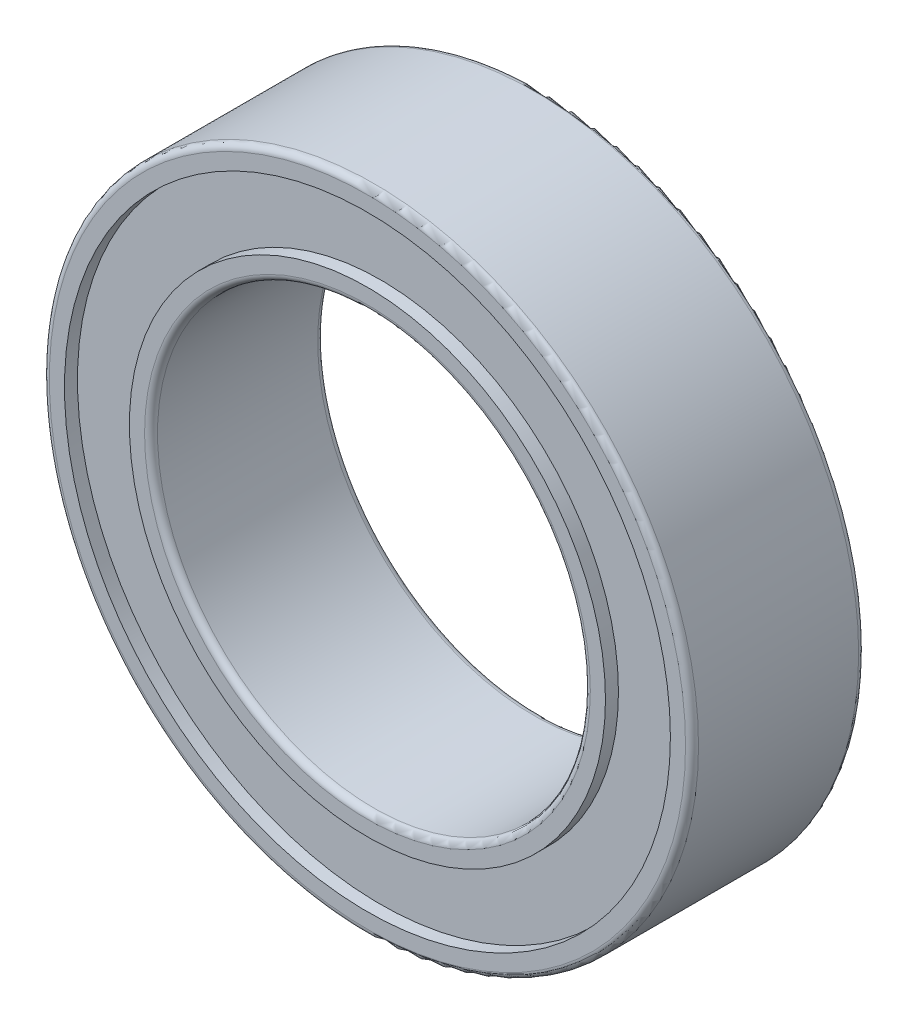
SolidWorks part; units mm, degrees
ref_plane "Front Plane" through (0, 0, 0) normal (0, 0, 1) x (1, 0, 0)
ref_plane "Top Plane" through (0, 0, 0) normal (0, 1, 0) x (1, 0, 0)
ref_plane "Right Plane" through (0, 0, 0) normal (1, 0, 0) x (0, 0, -1)
sketch "Sketch1" plane through (0, 0, 0) normal (0, 0, 1) x (1, 0, 0)
  circle A0 centre (0, 0) radius 5
  circle A1 centre (0, 0) radius 7.5
  dimension "D1" = 10
  dimension "D2" = 15
extrude "Boss-Extrude1" add sketch "Sketch1" along normal blind 4
sketch "Sketch2" plane through (0, 0, 4) normal (0, 0, 1) x (1, 0, 0)
  circle A2 centre (0, 0) radius 7
  circle A3 centre (0, 0) radius 7
  circle A5 centre (0, 0) radius 5.5
  circle A6 centre (0, 0) radius 5.5
  dimension "D1" = 0.5
  dimension "D2" = 0.5
extrude "Cut-Extrude1" cut sketch "Sketch2" against normal blind 0.3
extrude "Cut-Extrude2" cut sketch "Sketch2<2>" along normal blind 0.5 from surface starting at face at (7.5, 0, 0)
sketch "Sketch2<2>" plane through (0, 0, 4) normal (0, 0, 1) x (1, 0, 0) same geometry as "Sketch2"
fillet "Fillet1" radius 0.15 4 edges at (5, 0, 4) (7.5, 0, 4) (5, 0, 0) (7.5, 0, 0)
